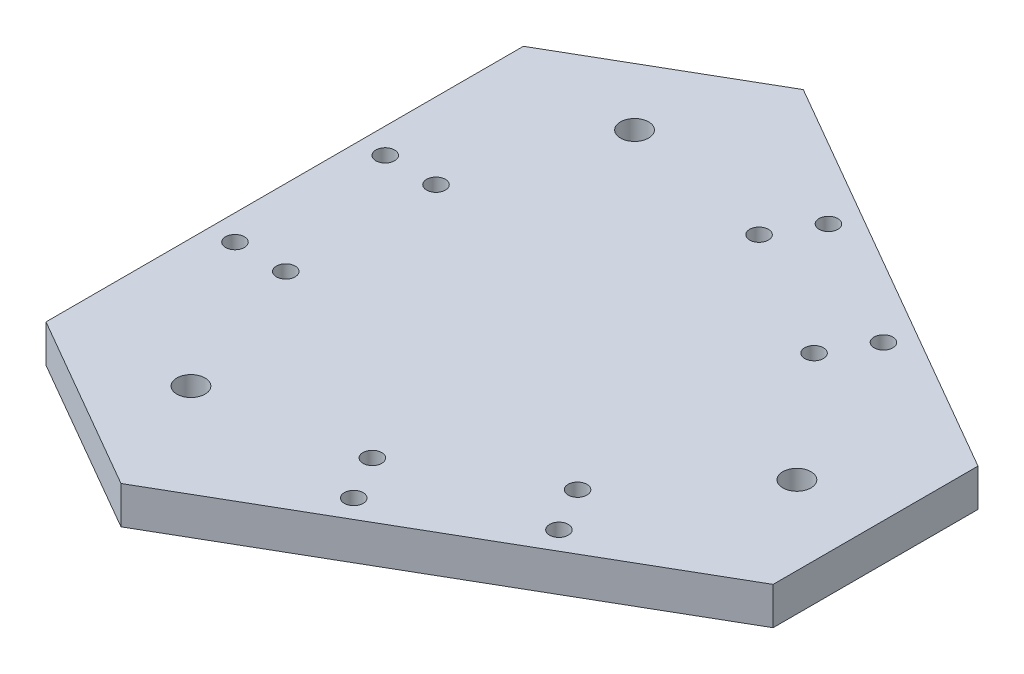
SolidWorks part; units mm, degrees
material "1060 Alloy"
ref_plane "Front Plane" through (0, 0, 0) normal (0, 0, 1) x (1, 0, 0)
ref_plane "Top Plane" through (0, 0, 0) normal (0, 1, 0) x (1, 0, 0)
ref_plane "Right Plane" through (0, 0, 0) normal (1, 0, 0) x (0, 0, -1)
sketch "Sketch2" plane through (0, 0, 0) normal (0, 1, 0) x (1, 0, 0)
  line L0 (-86.6025, 80.718) -> (-26.6025, 115.359) construction
  line L1 (173.2051, 0) -> (-86.6025, 150) construction
  line L2 (-86.6025, 150) -> (-86.6025, -150) construction
  line L3 (-86.6025, -150) -> (173.2051, 0) construction
  line L4 (0, 0) -> (43.3013, -75) construction
  line L5 (0, 0) -> (43.3013, 75) construction
  line L6 (0, 0) -> (-86.6025, 0) construction
  line L7 (-86.6025, -80.718) -> (-26.6025, -115.359) construction
  line L8 (113.2051, -34.641) -> (113.2051, 34.641) construction
  line L9 (-26.6025, 115.359) -> (-86.6025, 80.718)
  line L10 (-86.6025, 80.718) -> (-86.6025, -80.718)
  line L11 (-86.6025, -80.718) -> (-26.6025, -115.359)
  line L12 (-26.6025, -115.359) -> (113.2051, -34.641)
  line L13 (113.2051, -34.641) -> (113.2051, 34.641)
  line L14 (113.2051, 34.641) -> (-26.6025, 115.359)
  circle A0 centre (0, 0) radius 86.6025 construction
  point P15 (25.9808, -85)
  point P16 (60.6218, -65)
  point P17 (60.6218, 65)
  point P18 (25.9808, 85)
  point P19 (-86.6025, 20)
  point P20 (-86.6025, -20)
  dimension "D1" = 300
  dimension "D2" = 60
  dimension "D3" = 130
  dimension "D4" = 130
  dimension "D5" = 40
  dimension "D6" = 161.4359
extrude "Boss-Extrude1" add sketch "Sketch2" along normal blind 12.7
sketch "Sketch3" plane through (0, 0, 0) normal (0, -1, 0) x (1, 0, 0)
  line L0 (-26.6025, -115.359) -> (113.2051, -34.641) construction
  line L2 (0, 0) -> (43.3013, -75) construction
  line L3 (0, 0) -> (43.3013, 75) construction
  line L4 (0, 0) -> (-86.6025, 0) construction
  line L5 (-86.6025, -80.718) -> (-86.6025, 80.718) construction
  line L6 (-52.249, -50.8) -> (-86.6025, -50.8) construction
  line L7 (-52.249, -50.8) -> (-52.249, 50.8) construction
  line L8 (-52.249, 50.8) -> (-86.6025, 50.8) construction
  line L9 (-86.6025, -50.8) -> (-86.6025, 50.8) construction
  line L10 (-52.249, -50.8) -> (-86.6025, 50.8) construction
  line L11 (-52.249, 50.8) -> (-86.6025, -50.8) construction
  line L12 (-69.4258, 0) -> (-69.4258, -50.8) construction
  line L13 (-69.4258, -25.4) -> (-86.6025, -25.4) construction
  line L14 (0, 0) -> (86.6025, 0) construction
  circle A6 centre (-78.0142, -25.4) radius 3.175
  circle A7 centre (-60.8374, -25.4) radius 3.175
  circle A8 centre (-78.0142, 25.4) radius 3.175
  circle A9 centre (-60.8374, 25.4) radius 3.175
  circle A10 centre (61.0041, 54.8622) radius 3.175
  circle A11 centre (17.01, 80.2622) radius 3.175
  circle A12 centre (52.4158, 39.9867) radius 3.175
  circle A13 centre (8.4217, 65.3867) radius 3.175
  circle A14 centre (8.4217, -65.3867) radius 3.175
  circle A15 centre (17.01, -80.2622) radius 3.175
  circle A16 centre (61.0041, -54.8622) radius 3.175
  circle A17 centre (52.4158, -39.9867) radius 3.175
  circle A18 centre (0, 0) radius 86.6025 construction
  circle A19 centre (86.6025, 0) radius 4.7625
  circle A20 centre (-43.3013, 75) radius 4.7625
  circle A21 centre (-43.3013, -75) radius 4.7625
  point P2 (-69.4258, 0)
  point P24 (-69.4258, -25.4)
  dimension "D1" = 34.3535
  dimension "D3" = 6.35
  dimension "D2" = 101.6
extrude "Cut-Extrude1" cut sketch "Sketch3" against normal blind 20.32
